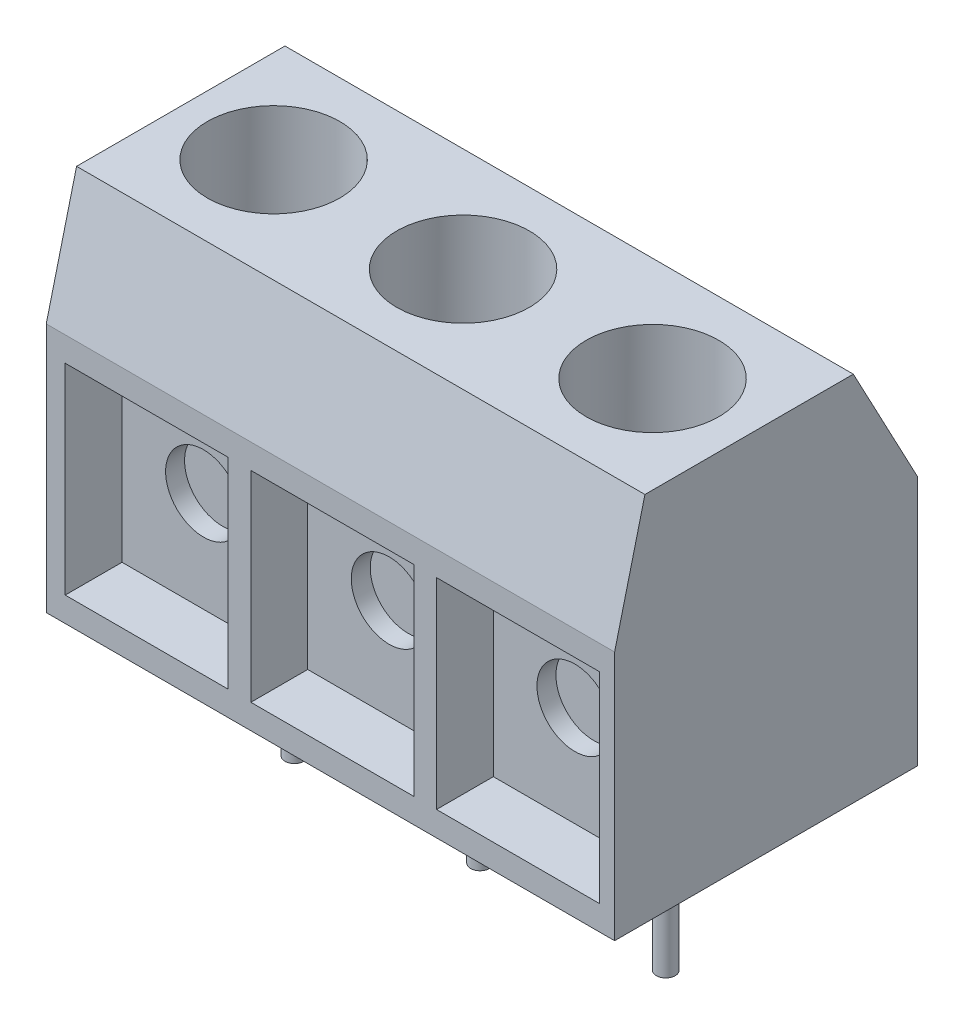
SolidWorks part; units mm, degrees
ref_plane "Alzado" through (0, 0, 0) normal (0, 0, 1) x (1, 0, 0)
ref_plane "Planta" through (0, 0, 0) normal (0, 1, 0) x (1, 0, 0)
ref_plane "Vista lateral" through (0, 0, 0) normal (1, 0, 0) x (0, 0, -1)
sketch "Croquis1" plane through (0, 0, 0) normal (0, 1, 0) x (1, 0, 0)
  line L1 (-7.5, 4) -> (7.5, 4)
  line L2 (-7.5, 4) -> (-7.5, -4)
  line L3 (-7.5, -4) -> (7.5, -4)
  line L4 (7.5, 4) -> (7.5, -4)
  line L5 (-7.5, 4) -> (7.5, -4) construction
  line L6 (-7.5, -4) -> (7.5, 4) construction
  point P0 (0, 0)
  dimension "D1" = 15
  dimension "D2" = 8
extrude "Saliente-Extruir1" add sketch "Croquis1" along normal blind 6.6
sketch "Croquis2" plane through (0, 0, 0) normal (1, 0, 0) x (0, 0, -1)
  line L0 (-4, 6.6) -> (4, 6.6)
  line L1 (-3.2, 9.8) -> (2.3, 9.8)
  line L2 (2.3, 9.8) -> (4, 6.6)
  line L3 (-4, 6.6) -> (-3.2, 9.8)
  line L4 (-4, 6.6) -> (4, 6.6) construction
  line L5 (-4, 0) -> (4, 0) construction
  point P6 (-3.1605, 9.3413)
  point P7 (0, 6.6)
  dimension "D1" = 0.8
  dimension "D2" = 5.5
  dimension "D3" = 8
  dimension "D4" = 9.8
extrude "Saliente-Extruir2" add sketch "Croquis2" along normal up to surface and the other way up to surface up to face at (7.5, 3.3, 0) other way up to face at (-7.5, 3.3, 0)
sketch "Croquis3" plane through (0, 9.8, 0) normal (0, 1, 0) x (1, 0, 0)
  line L0 (-7.5, -3.2) -> (-7.5, 2.3) construction
  line L1 (7.5, 2.3) -> (-7.5, 2.3) construction
  circle A0 centre (-5.05, -0.45) radius 1.75
  point P4 (0, 0)
  dimension "D1" = 3.5
  dimension "D2" = 2.45
  dimension "D3" = 2.75
extrude "Cortar-Extruir1" cut sketch "Croquis3" against normal blind 3
sketch "Croquis4" plane through (0, 6.8, 0) normal (0, 1, 0) x (1, 0, 0)
  line L0 (-5.05, -2.2) -> (-5.05, -0.45) construction
  line L1 (-3.3, -0.45) -> (-6.8, -0.45) construction
  line L2 (-4.8, -2.2) -> (-4.8, -0.7)
  line L3 (-3.3, -0.2) -> (-4.8, -0.2)
  line L4 (-5.3, -2.2) -> (-5.3, -0.7)
  line L5 (-3.3, -0.7) -> (-4.8, -0.7)
  line L6 (-4.8, -0.2) -> (-4.8, 1.2821)
  line L7 (-4.8, -2.2) -> (-4.8, 1.2821) construction
  line L8 (-5.3, -0.7) -> (-6.8, -0.7)
  line L9 (-3.3, -0.7) -> (-6.8, -0.7) construction
  line L10 (-5.3, -0.2) -> (-5.3, 1.2821)
  line L11 (-5.3, -2.2) -> (-5.3, 1.2821) construction
  line L12 (-5.3, -0.2) -> (-6.8, -0.2)
  line L13 (-3.3, -0.2) -> (-6.8, -0.2) construction
  line L15 (-5.05, -2.2) -> (-5.05, 1.2821) construction
  circle A1 centre (-5.05, -0.45) radius 1.75
  circle A2 centre (-5.05, -0.45) radius 1.75
  point P16 (0, 0)
  circle M4 centre (-5.05, -0.45) radius 1.75
  dimension "D1" = 0
  dimension "D2" = 0.25
  dimension "D3" = 0.25
extrude "Cortar-Extruir2" cut sketch "Croquis4" against normal blind 0.25 contours L10 L12 L8 L4 L2 L5 L3 L6 M4 region at (-5.05, 6.8, 0.45)
pattern_linear "MatrizL1" count 3 spacing 5 along (1, 0, 0) of "Cortar-Extruir1", "Cortar-Extruir2"
sketch "Croquis5" plane through (0, 0, 0) normal (0, -1, 0) x (1, 0, 0)
  line L0 (-7.5, -4) -> (-7.5, 4) construction
  circle A0 centre (-4.95, 0) radius 0.25
  point P4 (0, 0)
  dimension "D2" = 0.5
  dimension "D1" = 2.55
extrude "Saliente-Extruir3" add sketch "Croquis5" along normal blind 4
pattern_linear "MatrizL2" count 3 spacing 4.9 along (1, 0, 0) of "Saliente-Extruir3"
sketch "Croquis6" plane through (0, 0, 4) normal (0, 0, 1) x (1, 0, 0)
  line L0 (-7.5, 6.6) -> (-7.5, 0) construction
  line L1 (-7, 5.95) -> (-2.7, 5.95)
  line L2 (-7, 5.95) -> (-7, 0.65)
  line L3 (-7, 0.65) -> (-2.7, 0.65)
  line L4 (-2.7, 5.95) -> (-2.7, 0.65)
  line L5 (-7, 5.95) -> (-2.7, 0.65) construction
  line L6 (-7, 0.65) -> (-2.7, 5.95) construction
  circle A0 centre (-4.85, 3.3) radius 1
  point P0 (-4.85, 3.3)
  point P5 (-7.5, 3.3)
  dimension "D4" = 2
  dimension "D1" = 5.3
  dimension "D2" = 4.3
  dimension "D3" = 0.5
extrude "Cortar-Extruir3" cut sketch "Croquis6" against normal blind 1.5
extrude "Cortar-Extruir4" cut sketch "Croquis6<2>" against normal blind 2 contours A0 region at (-4.85, 3.3, 4)
sketch "Croquis6<2>" plane through (0, 0, 4) normal (0, 0, 1) x (1, 0, 0) same geometry as "Croquis6"
pattern_linear "MatrizL3" count 3 spacing 4.9 along (1, 0, 0) of "Cortar-Extruir3", "Cortar-Extruir4"
